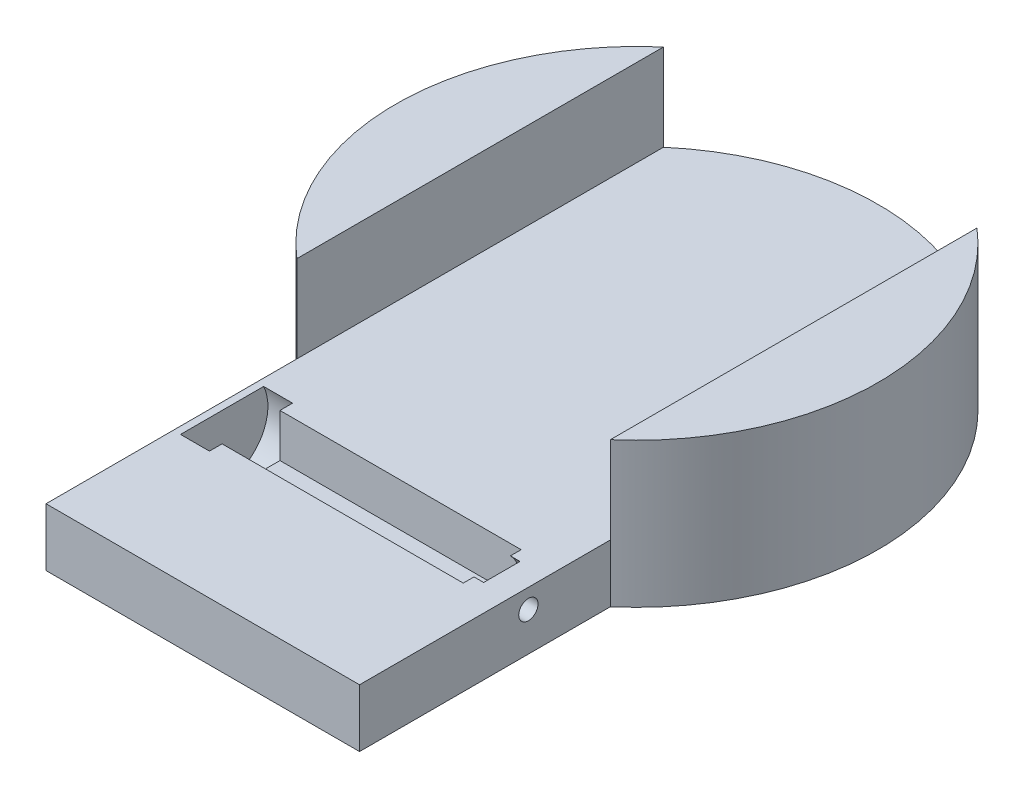
SolidWorks part; units mm, degrees
ref_plane "Front Plane" through (0, 0, 0) normal (0, 0, 1) x (1, 0, 0)
ref_plane "Top Plane" through (0, 0, 0) normal (0, 1, 0) x (1, 0, 0)
ref_plane "Right Plane" through (0, 0, 0) normal (1, 0, 0) x (0, 0, -1)
sketch "Sketch1" plane through (0, 0, 0) normal (0, 1, 0) x (1, 0, 0)
  circle A0 centre (0, 0) radius 50
  dimension "D1" = 100
extrude "Boss-Extrude1" add sketch "Sketch1" along normal blind 30
sketch "Sketch2" plane through (0, 0, 0) normal (0, -1, 0) x (1, 0, 0)
  line L0 (-2, 1.5) -> (-2, -1.5)
  circle A0 centre (0, 0) radius 4.4
  circle A1 centre (0, 0) radius 2.5
  dimension "D1" = 8.8
  dimension "D2" = 5
  dimension "D3" = 2
extrude "Boss-Extrude2" add sketch "Sketch2" along normal blind 10 contours A0 A1 | L0 A1 region at (-2.2018, 0, 0) region at (-4.2755, 0, 0)
sketch "Sketch3" plane through (0, 0, 0) normal (0, -1, 0) x (1, 0, 0)
  circle A0 centre (0, 0) radius 7.5
  circle A1 centre (0, 0) radius 4.4
  circle M2 centre (0, 0) radius 4.4
  dimension "D1" = 15
extrude "Boss-Extrude3" add sketch "Sketch3" along normal blind 2 contours A0 M2 region at (-7.2879, 0, 0)
sketch "Sketch4" plane through (0, 30, 0) normal (0, 1, 0) x (1, 0, 0)
  line L1 (32.5, 50) -> (-32.5, 50)
  line L2 (32.5, 50) -> (32.5, -50)
  line L4 (-32.5, 50) -> (-32.5, -50)
  line L5 (32.5, 50) -> (-32.5, -50) construction
  line L6 (32.5, -50) -> (-32.5, 50) construction
  line L8 (-32.5, -50) -> (32.5, -50)
  point P0 (0, 0)
  dimension "D1" = 65
  dimension "D2" = 100
extrude "Cut-Extrude1" cut sketch "Sketch4" against normal offset from surface (18 mm away) 12 up to face at (0, 0, 7.5)
ref_plane "Plane1" through (0, 12, 50) normal (0, 0, 1) x (1, 0, 0)
sketch "Sketch5" plane through (0, 12, 50) normal (0, 0, 1) x (1, 0, 0)
  line L0 (-50, -12) -> (50, -12) construction
  line L1 (-32.5, 0) -> (32.5, 0)
  line L2 (-32.5, 0) -> (-32.5, -12)
  line L3 (-32.5, -12) -> (32.5, -12)
  line L4 (32.5, 0) -> (32.5, -12)
  line L5 (-32.5, 0) -> (32.5, -12) construction
  line L6 (-32.5, -12) -> (32.5, 0) construction
  point P4 (0, -6)
extrude "Boss-Extrude4" add sketch "Sketch5" along normal blind 40 separate body
sketch "Sketch6" plane through (0, 0, 50) normal (0, 0, -1) x (-1, 0, 0)
  line L1 (-32.5, 12) -> (32.5, 12)
  line L2 (-32.5, 12) -> (-32.5, 0)
  line L3 (-32.5, 0) -> (32.5, 0)
  line L4 (32.5, 12) -> (32.5, 0)
  line L5 (-32.5, 12) -> (32.5, 0) construction
  line L6 (-32.5, 0) -> (32.5, 12) construction
  point P4 (0, 6)
extrude "Boss-Extrude5" add sketch "Sketch6" along normal up to surface up to face at (0, 21, 0)
sketch "Sketch7" plane through (0, 12, 0) normal (0, 1, 0) x (1, 0, 0)
  line L0 (0, 0) -> (0, -90) construction
  line L1 (25, -49) -> (-25, -49)
  line L2 (25, -49) -> (25, -61)
  line L3 (25, -61) -> (-25, -61)
  line L4 (-25, -49) -> (-25, -61)
  line L5 (25, -49) -> (-25, -61) construction
  line L6 (25, -61) -> (-25, -49) construction
  line L7 (32.5, -90) -> (-32.5, -90) construction
  point P0 (0, -55)
  point P10 (0, 0)
  dimension "D1" = 50
  dimension "D2" = 55
  dimension "D3" = 12
extrude "Cut-Extrude2" cut sketch "Sketch7" against normal offset from surface (9 mm away) 3 up to face at (0.25, 0, 0)
sketch "Sketch8" plane through (-25, 0, 0) normal (1, 0, 0) x (0, 0, -1)
  circle A0 centre (-55, 8) radius 9.5
  dimension "D1" = 19
extrude "Cut-Extrude3" cut sketch "Sketch8" against normal blind 6
sketch "Sketch9" plane through (25, 0, 0) normal (-1, 0, 0) x (0, 0, 1)
  circle A0 centre (55, 8) radius 2
  dimension "D1" = 4
extrude "Cut-Extrude4" cut sketch "Sketch9" against normal up to surface (7.5 mm away) up to face at (32.5, 6, 63.9984)
sketch "Sketch10" plane through (25, 0, 0) normal (-1, 0, 0) x (0, 0, 1)
  circle A0 centre (55, 8) radius 5.5
  dimension "D1" = 11
extrude "Cut-Extrude5" cut sketch "Sketch10" against normal blind 2 and the other way blind 1
sketch "Sketch11" plane through (32.5, 0, 0) normal (1, 0, 0) x (0, 0, -1)
  circle A0 centre (-55, 8) radius 12 construction
  dimension "D1" = 24
